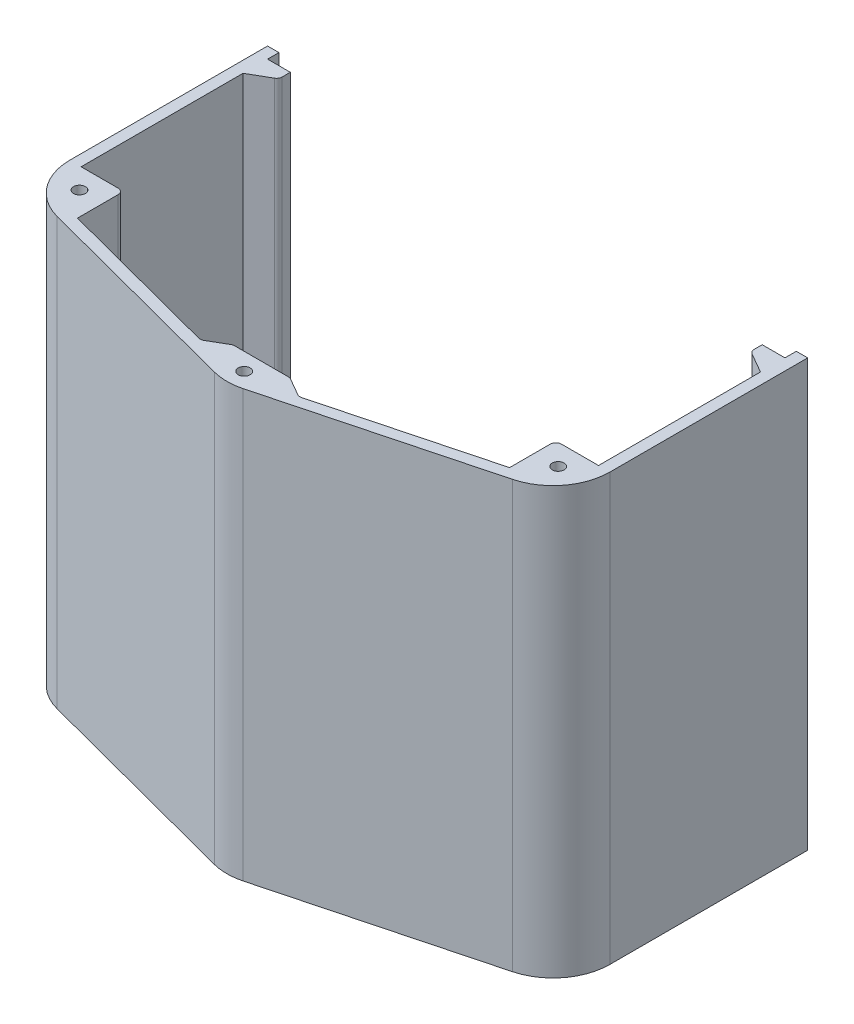
SolidWorks part; units mm, degrees
ref_plane "Front Plane" through (0, 0, 0) normal (0, 0, 1) x (1, 0, 0)
ref_plane "Top Plane" through (0, 0, 0) normal (0, 1, 0) x (1, 0, 0)
ref_plane "Right Plane" through (0, 0, 0) normal (1, 0, 0) x (0, 0, -1)
sketch "Sketch1" plane through (0, 0, 0) normal (0, 1, 0) x (1, 0, 0)
  line L0 (0, 0) -> (0, -110)
  line L2 (95, 0) -> (95, -69.5822)
  line L3 (80.0899, -88.9237) -> (5.0899, -108.6606)
  line L4 (-95, 0) -> (95, 0)
  line L5 (-95, 0) -> (-95, -69.5822)
  line L6 (-80.0899, -88.9237) -> (-5.0899, -108.6606)
  arc A0 (5.0899, -108.6606) -> (-5.0899, -108.6606) centre (0, -89.3191) cw
  arc A1 (95, -69.5822) -> (80.0899, -88.9237) centre (75, -69.5822) cw
  arc A2 (-95, -69.5822) -> (-80.0899, -88.9237) centre (-75, -69.5822) ccw
  point P12 (95, -85)
  point P15 (-95, -85)
  dimension "D7" = 20
  dimension "D1" = 110
  dimension "D2" = 95
  dimension "D3" = 85
  dimension "D4" = 85
  dimension "D5" = 95
  dimension "D6" = 190
extrude "Boss-Extrude1" add sketch "Sketch1" along normal blind 150 contours L6 A0 L3 A1 L2 L4 L5 A2
shell "Shell2" thickness 4 removed face at (0, 0, 67.5089) removed face at (0, 75, 0) removed face at (0, 150, 67.5089)
sketch "Sketch3" plane through (0, 0, 0) normal (0, 1, 0) x (1, 0, 0)
  line L0 (-91, 0) -> (-91, -4) construction
  line L1 (-91, 0) -> (-91, -69.5822) construction
  line L2 (-91, -4) -> (-83, -4)
  line L3 (-83, -4) -> (-83, -8)
  line L4 (-83, -8) -> (-91, -12.6188)
  line L5 (-91, -69.5822) -> (-76, -69.5822)
  line L9 (-95, -69.5822) -> (-91, -69.5822)
  line L10 (-91, -12.6188) -> (-91, -4)
  line L11 (-76, -69.5822) -> (-76, -85.8638)
  line L12 (-79.0719, -85.0554) -> (-4.0719, -104.7923) construction
  line L13 (-76, -85.8638) -> (-80.3003, -88.8671)
  line L14 (-95, -69.5822) -> (-90.8398, -81.7929)
  line L15 (-90.8398, -81.7929) -> (-80.3003, -88.8671)
  line L16 (0, -60.1255) -> (0, 60.1255) construction
  line L17 (91, -69.5822) -> (76, -69.5822)
  line L18 (76, -69.5822) -> (76, -85.8638)
  line L19 (76, -85.8638) -> (80.3003, -88.8671)
  line L20 (90.8398, -81.7929) -> (80.3003, -88.8671)
  line L21 (95, -69.5822) -> (90.8398, -81.7929)
  line L22 (95, -69.5822) -> (91, -69.5822)
  line L23 (83, -8) -> (91, -12.6188)
  line L24 (83, -4) -> (83, -8)
  line L25 (91, -4) -> (83, -4)
  line L26 (91, -12.6188) -> (91, -4)
  arc A1 (-95, -69.5822) -> (-80.0899, -88.9237) centre (-75, -69.5822) ccw construction
  dimension "D1" = 4
  dimension "D2" = 8
  dimension "D3" = 4
  dimension "D4" = 15
  dimension "D5" = 90
  dimension "D6" = 120
extrude "Boss-Extrude2" add sketch "Sketch3" along normal blind 150
fillet "Fillet1" radius 2 4 edges at (83, 75, 8) (-83, 75, 8) (-76, 75, 69.5822) (76, 75, 69.5822)
sketch "Sketch4" plane through (0, 0, 0) normal (0, 1, 0) x (1, 0, 0)
  line L0 (-91, -69.5822) -> (-76, -85.8638) construction
  line L1 (-84.1973, -76.9662) -> (-76.5858, -70.168) construction
  line L2 (76, -85.8638) -> (91, -69.5822) construction
  line L3 (84.1973, -76.9662) -> (76.5858, -70.168) construction
  arc A0 (-76, -71.5822) -> (-78, -69.5822) centre (-78, -71.5822) ccw construction
  arc A2 (78, -69.5822) -> (76, -71.5822) centre (78, -71.5822) ccw construction
  circle A4 centre (84.1973, -76.9662) radius 2.1
  circle A5 centre (-84.1973, -76.9662) radius 2.1
  dimension "D1" = 4.2
  dimension "D3" = 4.2
  dimension "D2" = 10.2054
extrude "Cut-Extrude1" cut sketch "Sketch4" along normal blind 150
sketch "Sketch5" plane through (0, 0, 0) normal (0, 1, 0) x (1, 0, 0)
  line L0 (-83, -4) -> (83, -4)
  line L1 (83, -4) -> (83, -6.8453)
  line L2 (83, -6.8453) -> (-83, -6.8453)
  line L3 (-83, -6.8453) -> (-83, -4)
extrude "Boss-Extrude3" add sketch "Sketch5" along normal blind 10
sketch "Sketch6" plane through (0, 0, 0) normal (0, 1, 0) x (1, 0, 0)
  line L0 (0, -101.1191) -> (0, -105.3191) construction
  line L1 (0, -101.1191) -> (0, -97.1191) construction
  line L2 (0, -60.1255) -> (0, 60.1255) construction
  line L4 (10, -97.1191) -> (17.2732, -101.3182)
  line L7 (10, -97.1191) -> (-10, -97.1191)
  line L8 (-10, -97.1191) -> (-17.2732, -101.3182)
  line L9 (-76, -85.8638) -> (-4.0719, -104.7923) construction
  line L16 (-17.2732, -101.3182) -> (0, -107.9721)
  line L17 (0, -107.9721) -> (17.2732, -101.3182)
  arc A0 (-4.0719, -104.7923) -> (4.0719, -104.7923) centre (0, -89.3191) ccw construction
  dimension "D1" = 4.2
  dimension "D2" = 4
  dimension "D3" = 10
  dimension "D5" = 150
extrude "Boss-Extrude6" add sketch "Sketch6" along normal blind 150
fillet "Fillet2" radius 2 4 edges at (17.2732, 75, 101.3182) (10, 75, 97.1191) (-17.2732, 75, 101.3182) (-10, 75, 97.1191)
sketch "Sketch7" plane through (0, 0, 0) normal (0, 1, 0) x (1, 0, 0)
  line L0 (0, -97.1191) -> (0, -103.2191) construction
  line L1 (9.4641, -97.1191) -> (-9.4641, -97.1191) construction
  circle A0 centre (0, -103.2191) radius 2.1
  dimension "D2" = 4.2
  dimension "D1" = 6.1
extrude "Cut-Extrude3" cut sketch "Sketch7" along normal blind 150
